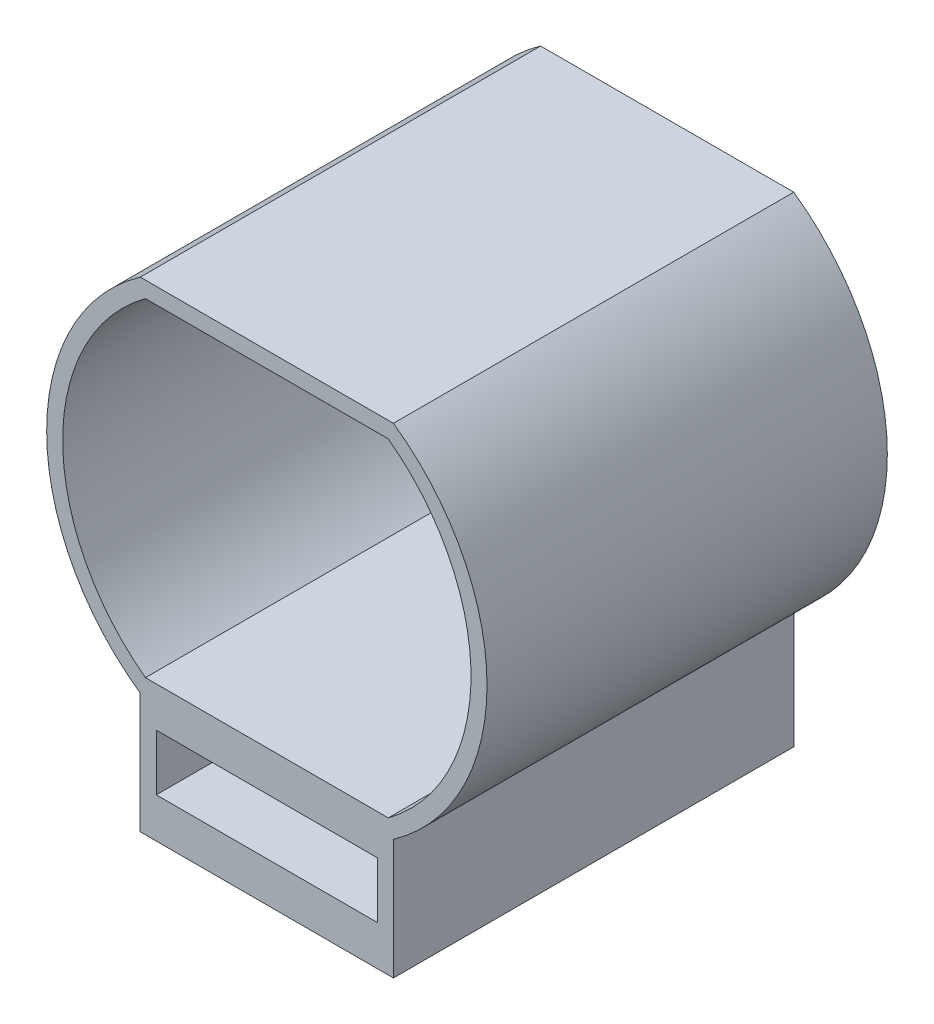
SolidWorks part; units mm, degrees
ref_plane "Front Plane" through (0, 0, 0) normal (0, 0, 1) x (1, 0, 0)
ref_plane "Top Plane" through (0, 0, 0) normal (0, 1, 0) x (1, 0, 0)
ref_plane "Right Plane" through (0, 0, 0) normal (1, 0, 0) x (0, 0, -1)
sketch "Sketch2" plane through (0, 0, 0) normal (0, 0, 1) x (1, 0, 0)
  line L3 (15.8114, 22.5) -> (-15.8114, 22.5)
  line L5 (15.8114, -22.5) -> (-15.8114, -22.5)
  arc A1 (15.8114, -22.5) -> (15.8114, 22.5) centre (0, 0) ccw
  arc A2 (-15.8114, 22.5) -> (-15.8114, -22.5) centre (0, 0) ccw
  circle A3 centre (0, 0) radius 4.75
extrude "Boss-Extrude8" add sketch "Sketch2" along normal blind 50
shell "Shell4" thickness 2 removed face at (4.75, 0, 50) removed face at (0, 0, 50)
sketch "Sketch3" plane through (0, 0, 2) normal (0, 0, 1) x (1, 0, 0)
  line L1 (-15.8114, -22.5) -> (15.8114, -22.5)
  line L2 (-15.8114, -22.5) -> (-15.8114, -37.5)
  line L3 (-15.8114, -37.5) -> (15.8114, -37.5)
  line L4 (15.8114, -22.5) -> (15.8114, -37.5)
  point P4 (0, 0)
  point P5 (0, 0)
extrude "Boss-Extrude9" add sketch "Sketch3" along normal up to vertex (48 mm away) and the other way up to vertex (2 mm away) contours L3 L4 L1 L2 up to point (15.8114, -22.5, 50) other way up to point (-15.8114, -22.5, 0)
sketch "Sketch4" plane through (0, 0, 50) normal (0, 0, 1) x (1, 0, 0)
  line L0 (0, -32.5) -> (0, -37.5)
  line L1 (-13.8114, -32.5) -> (13.8114, -32.5)
  line L2 (-13.8114, -32.5) -> (-13.8114, -25.5)
  line L3 (-13.8114, -25.5) -> (13.8114, -25.5)
  line L4 (13.8114, -32.5) -> (13.8114, -25.5)
  line L5 (-13.8114, -32.5) -> (13.8114, -25.5) construction
  line L6 (-13.8114, -25.5) -> (13.8114, -32.5) construction
  line L7 (-15.8114, -37.5) -> (15.8114, -37.5) construction
  line L8 (0, -25.5) -> (0, -20.5)
  line L9 (-15.1658, -20.5) -> (15.1658, -20.5) construction
  line L10 (-15.8114, -22.5) -> (-15.8114, -37.5) construction
  line L11 (-13.8114, -29) -> (-15.8114, -29)
  line L12 (13.8114, -29) -> (15.8114, -29)
  line L13 (15.8114, -22.5) -> (15.8114, -37.5) construction
  point P0 (0, -29)
  point P21 (0, 0)
extrude "Cut-Extrude1" cut sketch "Sketch4" against normal blind 10 contours L1 L4 L3 L2 region at (0, -29, 50)
